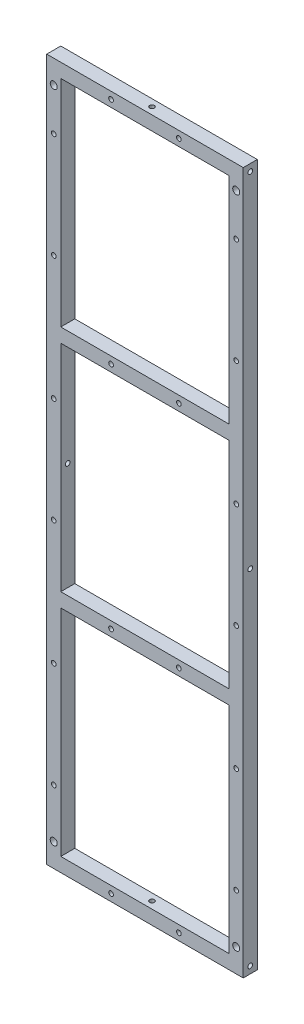
SolidWorks part; units mm, degrees
material "Alumina"
ref_plane "Front Plane" through (0, 0, 0) normal (0, 0, 1) x (1, 0, 0)
ref_plane "Top Plane" through (0, 0, 0) normal (0, 1, 0) x (1, 0, 0)
ref_plane "Right Plane" through (0, 0, 0) normal (1, 0, 0) x (0, 0, -1)
sketch "Sketch1" plane through (0, 0, 0) normal (0, 0, 1) x (1, 0, 0)
  line L0 (36, 144) -> (36, 52)
  line L9 (-42, -150) -> (42, -150)
  line L10 (-42, -150) -> (-42, 150)
  line L11 (-42, 150) -> (42, 150)
  line L12 (42, -150) -> (42, 150)
  line L13 (0, 0) -> (0, 46) construction
  line L15 (-36, -144) -> (36, -144)
  line L16 (-36, -144) -> (-36, -52)
  line L17 (-36, 144) -> (36, 144)
  line L21 (-36, 52) -> (36, 52)
  line L23 (-36, 46) -> (36, 46)
  line L25 (-36, -46) -> (36, -46)
  line L27 (-36, -52) -> (36, -52)
  line L33 (36, 46) -> (36, -46)
  line L34 (-36, 52) -> (-36, 144)
  line L35 (-36, -46) -> (-36, 46)
  line L36 (36, -52) -> (36, -144)
  dimension "D1" = 84
  dimension "D2" = 300
  dimension "D3" = 72
  dimension "D4" = 288
  dimension "D5" = 6
  dimension "D6" = 92
  dimension "D7" = 6
  dimension "D8" = 92
  dimension "D9" = 6
  dimension "D10" = 6
  dimension "D11" = 92
  dimension "D12" = 46
  dimension "D13" = 6
extrude "Boss-Extrude1" add sketch "Sketch1" along normal blind 6
sketch "Sketch2" plane through (42, 0, 0) normal (1, 0, 0) x (0, 0, -1)
  line L0 (-6, 150) -> (0, 150) construction
  line L1 (-6, -150) -> (-6, 150) construction
  line L3 (-3, 147) -> (-3, 0) construction
  circle A0 centre (-3, 147) radius 1
  circle A4 centre (-3, 0) radius 1
  circle A5 centre (-3, -147) radius 1
  circle A6 centre (-3, -294) radius 1
  dimension "D1" = 3
  dimension "D3" = 2
  dimension "D4" = 3
  dimension "D2" = 4
  dimension "D5" = 147
extrude "Cut-Extrude1" cut sketch "Sketch2" against normal blind 10
mirror "Mirror1" about plane through (0, 0, 0) normal (1, 0, 0) of "Cut-Extrude1"
sketch "Sketch4" plane through (0, 0, 6) normal (0, 0, 1) x (1, 0, 0)
  line L0 (-42, -150) -> (-42, 150) construction
  line L1 (42, -150) -> (42, 150) construction
  line L2 (-42, 150) -> (42, 150) construction
  line L3 (42, 150) -> (-42, 150) construction
  line L4 (-14.5, 147) -> (-14.5, 49) construction
  line L6 (-39, 122) -> (39, 122) construction
  line L7 (-39, 122) -> (-39, 77) construction
  line L8 (-39, 122) -> (-39, 24) construction
  circle A0 centre (-14.5, 147) radius 1
  circle A1 centre (14.5, 147) radius 1
  circle A8 centre (-39, 122) radius 1
  circle A20 centre (-14.5, 49) radius 1
  circle A21 centre (14.5, 49) radius 1
  circle A22 centre (-14.5, -49) radius 1
  circle A23 centre (14.5, -49) radius 1
  circle A24 centre (-14.5, -147) radius 1
  circle A25 centre (14.5, -147) radius 1
  circle A29 centre (39, 122) radius 1
  circle A30 centre (39, 77) radius 1
  circle A31 centre (-39, 77) radius 1
  circle A32 centre (-39, 24) radius 1
  circle A33 centre (39, 24) radius 1
  circle A34 centre (39, -21) radius 1
  circle A35 centre (-39, -21) radius 1
  circle A36 centre (-39, -74) radius 1
  circle A37 centre (39, -74) radius 1
  circle A38 centre (39, -119) radius 1
  circle A39 centre (-39, -119) radius 1
  dimension "D1" = 27.5
  dimension "D4" = 78
  dimension "D7" = 45
  dimension "D10" = 2
  dimension "D11" = 2
  dimension "D3" = 3
  dimension "D6" = 3
  dimension "D14" = 2
  dimension "D15" = 2
  dimension "D16" = 98
  dimension "D2" = 27.5
  dimension "D5" = 28
  dimension "D9" = 3
  dimension "D13" = 98
  dimension "D12" = 4
  dimension "D8" = 2
extrude "Cut-Extrude3" cut sketch "Sketch4" against normal blind 10
sketch "Sketch5" plane through (0, 150, 0) normal (0, 1, 0) x (1, 0, 0)
  line L0 (42, -6) -> (-42, -6) construction
  circle A0 centre (0, -3) radius 1
  point P5 (0, -6)
  dimension "D1" = 3
  dimension "D2" = 2
extrude "Cut-Extrude4" cut sketch "Sketch5" against normal blind 10
mirror "Mirror2" about plane through (0, 0, 0) normal (0, 1, 0) of "Cut-Extrude4"
sketch "Sketch6" plane through (0, 0, 6) normal (0, 0, 1) x (1, 0, 0)
  line L0 (-42, 150) -> (-42, -150) construction
  line L1 (42, 150) -> (-42, 150) construction
  circle A0 centre (-39, 140) radius 1.5
  dimension "D1" = 3
  dimension "D2" = 3
  dimension "D3" = 10
extrude "Cut-Extrude5" cut sketch "Sketch6" against normal blind 10
pattern_linear "LPattern1" count 2 spacing 78 along (1, 0, 0) count 2 spacing 280 along (0, -1, 0) of "Cut-Extrude5"
